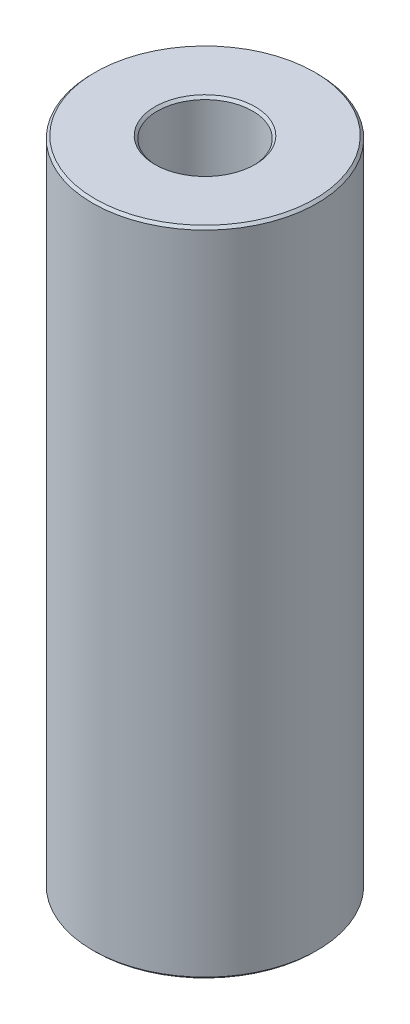
SolidWorks part; units mm, degrees
ref_plane "Front Plane" through (0, 0, 0) normal (0, 0, 1) x (1, 0, 0)
ref_plane "Top Plane" through (0, 0, 0) normal (0, 1, 0) x (1, 0, 0)
ref_plane "Right Plane" through (0, 0, 0) normal (1, 0, 0) x (0, 0, -1)
sketch "Sketch1" plane through (0, 0, 0) normal (0, 1, 0) x (1, 0, 0)
  circle A0 centre (0, 0) radius 17.5
  dimension "SLEEVE_OD" = 35
extrude "Boss-Extrude1" add sketch "Sketch1" along normal blind 101.6147
sketch "Sketch2" plane through (0, 0, 0) normal (0, 1, 0) x (1, 0, 0)
  circle A0 centre (0, 0) radius 7.4222
  dimension "BORE_D" = 14.8443
extrude "Cut-Extrude1" cut sketch "Sketch2" along normal through all
chamfer "Chamfer1" distance 0.3872 angle 45 4 edges at (0, 101.6147, 7.4222) (0, 0, 7.4222) (0, 0, 17.5) (0, 101.6147, 17.5)
